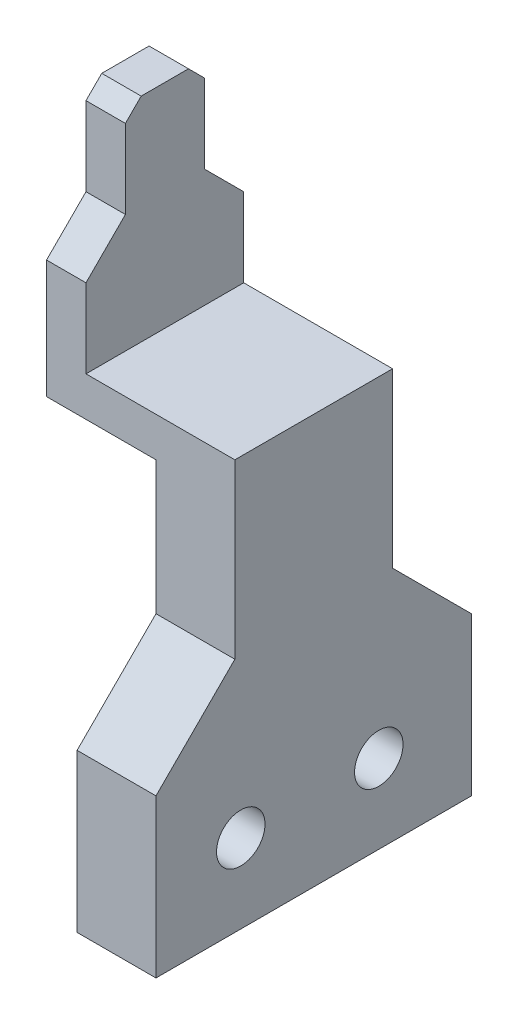
SolidWorks part; units mm, degrees
ref_plane "前视基准面" through (0, 0, 0) normal (0, 0, 1) x (1, 0, 0)
ref_plane "上视基准面" through (0, 0, 0) normal (0, 1, 0) x (1, 0, 0)
ref_plane "右视基准面" through (0, 0, 0) normal (1, 0, 0) x (0, 0, -1)
sketch "草图1" plane through (0, 0, 0) normal (1, 0, 0) x (0, 0, -1)
  line L1 (0, 0) -> (40, 0)
  line L2 (0, 0) -> (0, 20)
  line L3 (0, 20) -> (40, 20)
  line L4 (40, 0) -> (40, 20)
  dimension "D1" = 20
  dimension "D2" = 40
extrude "凸台-拉伸1" add sketch "草图1" along normal blind 10
sketch "草图2" plane through (10, 0, 0) normal (1, 0, 0) x (0, 0, -1)
  circle A0 centre (10.75, 10) radius 3.0738
  circle A1 centre (28.25, 10) radius 3.0738
extrude "切除-拉伸1" cut sketch "草图2" against normal blind 10
sketch "草图4" plane through (0, 0, 0) normal (0, 0, 1) x (1, 0, 0)
  line L0 (10, 20) -> (10, 51.899)
  line L1 (10, 51.899) -> (-8.875, 51.899)
  line L2 (-8.875, 78.899) -> (-13.875, 78.899)
  line L3 (-8.875, 81.899) -> (-8.875, 61.899) construction
  line L4 (-8.875, 78.899) -> (-8.875, 51.899)
  line L5 (-13.875, 78.899) -> (-13.875, 46.899)
  line L6 (-13.875, 46.899) -> (0, 46.899)
  line L7 (0, 46.899) -> (0, 20)
  line L8 (0, 20) -> (10, 20)
  line L9 (1.125, 61.899) -> (31.125, 61.899) construction
  line L10 (-28.875, 81.899) -> (-8.875, 81.899) construction
  dimension "D1" = 5
  dimension "D2" = 10
  dimension "D3" = 3
  dimension "D4" = 5
extrude "凸台-拉伸2" add sketch "草图4" against normal up to surface (40 mm away) up to face at (5, 10, -40)
sketch "草图5" plane through (10, 0, 0) normal (1, 0, 0) x (0, 0, -1)
  line L0 (-5.9633, 10) -> (44.7885, 10) construction
  line L2 (0, 20) -> (10, 20)
  line L3 (0, 51.899) -> (0, 0) construction
  line L4 (40, 0) -> (40, 51.899) construction
  line L5 (10, 20) -> (10, 78.899)
  line L6 (40, 78.899) -> (0, 78.899) construction
  line L7 (10, 78.899) -> (0, 78.899)
  line L8 (0, 78.899) -> (0, 20)
  line L9 (40, 20) -> (40, 78.899)
  line L10 (40, 78.899) -> (30, 78.899)
  line L11 (30, 78.899) -> (30, 20)
  line L12 (30, 20) -> (40, 20)
  dimension "D1" = 10
  dimension "D2" = 10
  dimension "D3" = 10
extrude "切除-拉伸2" cut sketch "草图5" against normal through all
chamfer "倒角1" distance 10 angle 45 2 edges at (5, 20, -30) (5, 20, -10)
sketch "草图6" plane through (10, 0, 0) normal (1, 0, 0) x (0, 0, -1)
  line L0 (10, 61.899) -> (15, 61.899)
  line L1 (10, 51.899) -> (10, 78.899) construction
  line L2 (-527.0391, 61.899) -> (472.9609, 61.899) construction
  line L3 (15, 61.899) -> (15, 78.899)
  line L4 (30, 78.899) -> (10, 78.899) construction
  line L5 (15, 78.899) -> (10, 78.899)
  line L6 (10, 78.899) -> (10, 61.899)
  line L7 (30, 61.899) -> (30, 78.899)
  line L8 (30, 78.899) -> (30, 51.899) construction
  line L9 (30, 78.899) -> (25, 78.899)
  line L10 (25, 78.899) -> (25, 61.899)
  line L11 (25, 61.899) -> (30, 61.899)
  dimension "D1" = 5
  dimension "D2" = 5
extrude "切除-拉伸3" cut sketch "草图6" against normal through all
chamfer "倒角3" distance 5 angle 45 2 edges at (-11.375, 61.899, -15) (-11.375, 61.899, -25)
chamfer "倒角4" distance 2 angle 45 2 edges at (-11.375, 78.899, -15) (-11.375, 78.899, -25)
